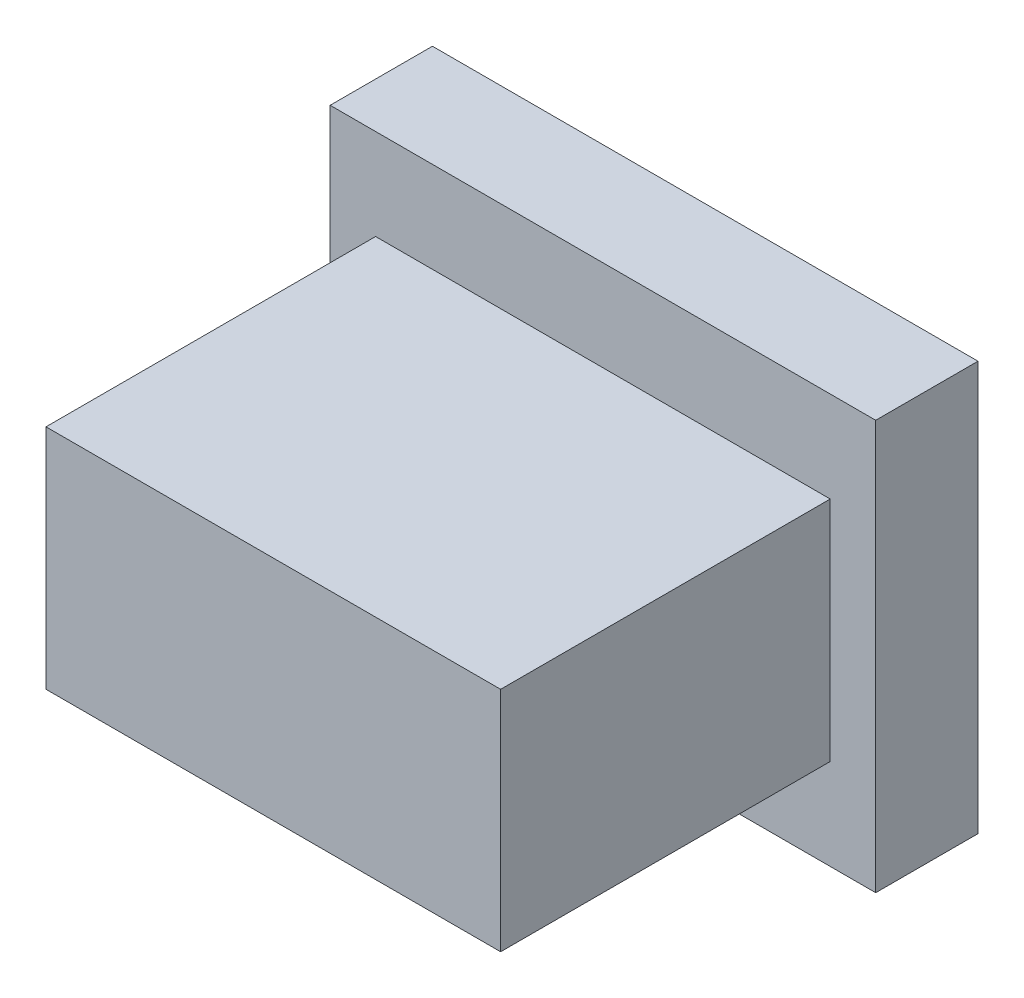
SolidWorks part; units mm, degrees
ref_plane "Front Plane" through (0, 0, 0) normal (0, 0, 1) x (1, 0, 0)
ref_plane "Top Plane" through (0, 0, 0) normal (0, 1, 0) x (1, 0, 0)
ref_plane "Right Plane" through (0, 0, 0) normal (1, 0, 0) x (0, 0, -1)
sketch "Sketch1" plane through (0, 0, 0) normal (0, 0, 1) x (1, 0, 0)
  line L0 (5, 0) -> (5, -2) construction
  line L1 (0, 0) -> (10, 0)
  line L2 (0, 0) -> (0, 5)
  line L3 (0, 5) -> (10, 5)
  line L4 (10, 0) -> (10, 5)
  line L5 (-1, -2) -> (11, -2)
  line L6 (-1, -2) -> (-1, 7)
  line L7 (-1, 7) -> (11, 7)
  line L8 (11, -2) -> (11, 7)
  line L9 (5, 5) -> (5, 7) construction
  line L10 (0, 2.5) -> (-1, 2.5) construction
  line L11 (11, 2.5) -> (10, 2.5) construction
  dimension "D1" = 10
  dimension "D2" = 5
  dimension "D3" = 1
  dimension "D4" = 1
  dimension "D5" = 2
extrude "Boss-Extrude1" add sketch "Sketch1" along normal blind 2.25 contours L5 L8 L7 L6 L4 L1 L2 L3 region at (-0.85, 2.5, 0)
extrude "Boss-Extrude2" add sketch "Sketch1<3>" along normal blind 9.5 contours L1 L4 L3 L2 region at (5, 2.5, 0)
sketch "Sketch1<3>" plane through (0, 0, 0) normal (0, 0, 1) x (1, 0, 0) same geometry as "Sketch1"
